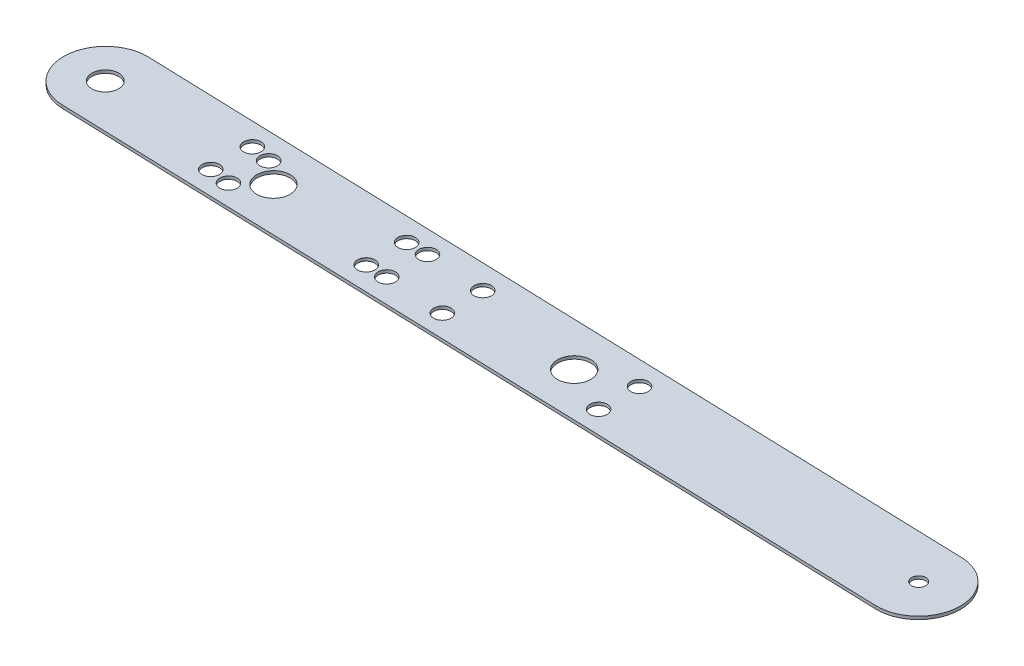
SolidWorks part; units mm, degrees
ref_plane "Front Plane" through (0, 0, 0) normal (0, 0, 1) x (1, 0, 0)
ref_plane "Top Plane" through (0, 0, 0) normal (0, 1, 0) x (1, 0, 0)
ref_plane "Right Plane" through (0, 0, 0) normal (1, 0, 0) x (0, 0, -1)
sketch "Sketch1" plane through (0, 0, 0) normal (0, 0, 1) x (1, 0, 0)
  line L0 (-78.6419, 31.6975) -> (161.4349, 101.4339) construction
  line L1 (-82.1287, 43.7013) -> (157.948, 113.4377)
  line L2 (-75.1551, 19.6937) -> (164.9217, 89.43)
  line L3 (-82.1287, 43.7013) -> (-75.1551, 19.6937) construction
  arc A0 (-82.1287, 43.7013) -> (-75.1551, 19.6937) centre (-78.6419, 31.6975) ccw
  arc A1 (164.9217, 89.43) -> (157.948, 113.4377) centre (161.4349, 101.4339) ccw
  point P2 (41.3965, 66.5657)
base flange "Base-Flange1" sketch "Sketch1" thickness 0.9 reverse thickness direction no parameters "D1"=1
sketch "Sketch7" plane through (0, 0, 0) normal (0, 0, 1) x (1, 0, 0)
  line L0 (-75.1551, 19.6937) -> (-82.1287, 43.7013) construction
  circle A0 centre (-78.6419, 31.6975) radius 1.75
extrude "Cut-Extrude1" cut sketch "Sketch7" against normal blind 10
hole_wizard "#6 (0.204) Diameter Slot1" positions "Sketch9" profile "Sketch8" size "#6" standard "ANSI Inch" slot yes end condition through all
sketch "Sketch9" plane through (0, 0, 0) normal (0, 0, 1) x (1, 0, 0)
  point P0 (-34.2115, 39.2524)
sketch "Sketch8" plane through (-34.2115, 39.2524, 0) normal (1, 0, 0) x (0, -1, 0)
  line L0 (0, 0) -> (0, 0.9)
  line L1 (0, 0.9) -> (2.5908, 0.9)
  line L2 (2.5908, 0.9) -> (2.5908, 0)
  line L5 (2.5908, 0) -> (0, 0)
  line L11 (0, -6.35) -> (0, 107.95) construction
  dimension "Thru Hole Dia." = 5.1816
  dimension "Thru Hole Depth" = 0.9
sketch "Sketch12" plane through (0, 0, -0.9) normal (0, 0, -1) x (-1, 0, 0)
  circle A0 centre (23.0553, 47.8102) radius 3.7522
hole_wizard "Ø1.0mm Dowel Slot1" positions "Sketch14" profile "Sketch13" size "Ø1.0" standard "ANSI Metric" slot yes end condition through all
sketch "Sketch14" plane through (0, 0, 0) normal (0, 0, 1) x (1, 0, 0)
  point P0 (-78.6419, 31.6975)
  point P3 (-78.6419, 31.6975)
sketch "Sketch13" plane through (-78.6419, 31.6975, 0) normal (1, 0, 0) x (0, -1, 0)
  line L0 (0, 0) -> (0, 0.9)
  line L1 (0, 0.9) -> (4, 0.9)
  line L2 (4, 0.9) -> (4, 0)
  line L5 (4, 0) -> (0, 0)
  line L11 (0, -6.35) -> (0, 107.95) construction
  dimension "Thru Hole Dia." = 8
  dimension "Thru Hole Depth" = 0.9
sketch "Sketch17" plane through (0, 0, 0) normal (0, 0, 1) x (1, 0, 0)
  circle A0 centre (39.3364, 65.6136) radius 3.75
hole_wizard "#19 (0.166) Diameter Slot2" positions "Sketch20" profile "Sketch19" size "#19" standard "ANSI Inch" slot yes end condition through all
sketch "Sketch20" plane through (0, 0, 0) normal (0, 0, 1) x (1, 0, 0)
  point P0 (161.4349, 101.4339)
sketch "Sketch19" plane through (161.4349, 101.4339, 0) normal (1, 0, 0) x (0, -1, 0)
  line L0 (0, 0) -> (0, 0.9)
  line L1 (0, 0.9) -> (2.1082, 0.9)
  line L2 (2.1082, 0.9) -> (2.1082, 0)
  line L5 (2.1082, 0) -> (0, 0)
  line L11 (0, -6.35) -> (0, 107.95) construction
  dimension "Thru Hole Dia." = 4.2164
  dimension "Thru Hole Depth" = 0.9
hole_wizard "Ø10.0mm Dowel Slot1" positions "Sketch22" profile "Sketch21" size "Ø10.0" standard "ANSI Metric" slot yes end condition through all
sketch "Sketch22" plane through (0, 0, -0.9) normal (0, 0, -1) x (-1, 0, 0)
  line L2 (90.6457, 28.2107) -> (-173.4387, 104.9207)
  circle A0 centre (78.6419, 31.6975) radius 4 construction
  arc A1 (75.1551, 19.6937) -> (82.1287, 43.7013) centre (78.6419, 31.6975) ccw construction
  arc A2 (-157.948, 113.4377) -> (-164.9217, 89.43) centre (-161.4349, 101.4339) ccw construction
  point P24 (28.994, 46.119)
  point P25 (-59.7569, 71.8989)
  dimension "D2" = 51.7
sketch "Sketch21" plane through (-28.994, 46.119, -0.9) normal (1, 0, 0) x (0, 1, 0)
  line L0 (0, 0) -> (0, 0.9)
  line L1 (0, 0.9) -> (5, 0.9)
  line L2 (5, 0.9) -> (5, 0)
  line L5 (5, 0) -> (0, 0)
  line L11 (0, -6.35) -> (0, 107.95) construction
  dimension "Thru Hole Dia." = 10
  dimension "Thru Hole Depth" = 0.9
hole_wizard "#6 (0.204) Diameter Slot7" positions "Sketch26" profile "Sketch25" size "#6" standard "ANSI Inch" slot yes end condition through all
sketch "Sketch26" plane through (0, 0, -0.9) normal (0, 0, -1) x (-1, 0, 0)
  point P0 (37.4542, 50.4528)
sketch "Sketch25" plane through (-37.4542, 50.4528, -0.9) normal (1, 0, 0) x (0, 1, 0)
  line L0 (0, 0) -> (0, 0.9)
  line L1 (0, 0.9) -> (2.5908, 0.9)
  line L2 (2.5908, 0.9) -> (2.5908, 0)
  line L5 (2.5908, 0) -> (0, 0)
  line L11 (0, -6.35) -> (0, 107.95) construction
  dimension "Thru Hole Dia." = 5.1816
  dimension "Thru Hole Depth" = 0.9
hole_wizard "#6 (0.204) Diameter Slot9" positions "Sketch30" profile "Sketch29" size "#6" standard "ANSI Inch" slot yes end condition through all
sketch "Sketch30" plane through (0, 0, 0) normal (0, 0, 1) x (1, 0, 0)
  point P0 (28.6223, 56.9997)
  point P2 (25.3744, 68.2854)
  point P4 (74.7726, 70.2473)
  point P6 (71.479, 81.6873)
sketch "Sketch29" plane through (28.6223, 56.9997, 0) normal (1, 0, 0) x (0, -1, 0)
  line L0 (0, 0) -> (0, 0.9)
  line L1 (0, 0.9) -> (2.5908, 0.9)
  line L2 (2.5908, 0.9) -> (2.5908, 0)
  line L5 (2.5908, 0) -> (0, 0)
  line L11 (0, -6.35) -> (0, 107.95) construction
  dimension "Thru Hole Dia." = 5.1816
  dimension "Thru Hole Depth" = 0.9
hole_wizard "#6 (0.204) Diameter Slot10" positions "Sketch32" profile "Sketch31" size "#6" standard "ANSI Inch" slot yes end condition through all
sketch "Sketch32" plane through (0, 0, -0.9) normal (0, 0, -1) x (-1, 0, 0)
  point P0 (-8.5953, 62.8981)
  point P2 (-11.9118, 51.6025)
sketch "Sketch31" plane through (8.5953, 62.8981, -0.9) normal (1, 0, 0) x (0, 1, 0)
  line L0 (0, 0) -> (0, 0.9)
  line L1 (0, 0.9) -> (2.5908, 0.9)
  line L2 (2.5908, 0.9) -> (2.5908, 0)
  line L5 (2.5908, 0) -> (0, 0)
  line L11 (0, -6.35) -> (0, 107.95) construction
  dimension "Thru Hole Dia." = 5.1816
  dimension "Thru Hole Depth" = 0.9
move or copy body "Body-Move/Copy1" bodies to move or copy 115 copy no rotation origin (0, 66.5657, -0.45) rotation axis (1, 0, 0) rotation angle 90
move or copy body "Body-Move/Copy2" bodies to move or copy 116 copy no rotation origin (39.0674, -1.3406, -0.1537) rotation axis (0.0343, 0.9994, -0.0044) rotation angle 14.509
sketch "Sketch33" plane through (0.1446, 66.1973, 0.5593) normal (-0.0022, -1, -0.0084) x (-1, 0.0022, 0)
  line L0 (84.0645, -7.7786) -> (83.3238, 17.2104) construction
  line L1 (83.3238, 17.2104) -> (-166.5664, 9.8034) construction
  arc A0 (84.0645, -7.7786) -> (83.3238, 17.2104) centre (83.6942, 4.7159) ccw construction
hole_wizard "#6 (0.204) Diameter Slot11" positions "Sketch35" profile "Sketch34" size "#6" standard "ANSI Inch" slot yes end condition through all
sketch "Sketch35" plane through (0.1446, 66.1973, 0.5593) normal (-0.0022, -1, -0.0084) x (-1, 0.0022, 0)
  point P0 (-2.4332, -3.6166)
  point P2 (-2.759, 8.1038)
  point P4 (45.2635, -2.2566)
  point P6 (44.814, 9.6774)
sketch "Sketch34" plane through (2.5778, 66.1614, 4.1757) normal (0.7071, -0.0075, 0.7071) x (0.7071, 0.0044, -0.7071)
  line L0 (0, 0) -> (0, 1.7505)
  line L1 (0, 1.7505) -> (2.5908, 1.7505)
  line L2 (2.5908, 1.7505) -> (2.5908, 0)
  line L5 (2.5908, 0) -> (0, 0)
  line L11 (0, -6.35) -> (0, 107.95) construction
  dimension "Thru Hole Dia." = 5.1816
  dimension "Thru Hole Depth" = 1.7505
sketch "Bend-Lines1" plane through (0, 0, 0) normal (0, 1, 0) x (1, 0, 0)
sketch "Bounding-Box1" plane through (0, 0, 0) normal (0, 1, 0) x (1, 0, 0)
sheet metal parameters "Sheet-Metal1" thickness 0.9 parameters "D1"=3
flat pattern "Flat-Pattern1" [suppressed]
sketch "Bend-Lines2" plane through (0, 0, 0) normal (0, 1, 0) x (1, 0, 0)
sketch "Bounding-Box2" [suppressed] plane through (0, 0, 0) normal (0, 1, 0) x (1, 0, 0)
sheet metal parameters "Sheet-Metal2" thickness 0.9 parameters "D1"=3
flat pattern "Flat-Pattern1"
sketch "Bend-Lines2" plane through (0, 0, 0) normal (0, 1, 0) x (1, 0, 0)
sketch "Bounding-Box2" [suppressed] plane through (0, 0, 0) normal (0, 1, 0) x (1, 0, 0)
sheet metal parameters "Sheet-Metal3" thickness 0.9 parameters "D1"=3
flat pattern "Flat-Pattern1"
sketch "Bend-Lines2" plane through (0, 0, 0) normal (0, 1, 0) x (1, 0, 0)
sketch "Bounding-Box2" [suppressed] plane through (0, 0, 0) normal (0, 1, 0) x (1, 0, 0)
sheet metal parameters "Sheet-Metal6" thickness 0.9 parameters "D1"=3
flat pattern "Flat-Pattern1"
sketch "Bend-Lines2" plane through (0, 0, 0) normal (0, 1, 0) x (1, 0, 0)
sketch "Bounding-Box2" [suppressed] plane through (0, 0, 0) normal (0, 1, 0) x (1, 0, 0)
sheet metal parameters "Sheet-Metal9" thickness 0.9 parameters "D1"=3
flat pattern "Flat-Pattern1"
sketch "Bend-Lines2" plane through (0, 0, 0) normal (0, 1, 0) x (1, 0, 0)
sketch "Bounding-Box2" [suppressed] plane through (0, 0, 0) normal (0, 1, 0) x (1, 0, 0)
sheet metal parameters "Sheet-Metal10" thickness 0.9 parameters "D1"=3
flat pattern "Flat-Pattern1"
sketch "Bend-Lines2" plane through (0, 0, 0) normal (0, 1, 0) x (1, 0, 0)
sketch "Bounding-Box2" [suppressed] plane through (0, 0, 0) normal (0, 1, 0) x (1, 0, 0)
sheet metal parameters "Sheet-Metal12" thickness 0.9 parameters "D1"=3
flat pattern "Flat-Pattern1"
sketch "Bend-Lines2" plane through (0, 0, 0) normal (0, 1, 0) x (1, 0, 0)
sketch "Bounding-Box2" [suppressed] plane through (0, 0, 0) normal (0, 1, 0) x (1, 0, 0)
sheet metal parameters "Sheet-Metal14" thickness 0.9 parameters "D1"=3
flat pattern "Flat-Pattern1"
sketch "Bend-Lines2" plane through (0, 0, 0) normal (0, 1, 0) x (1, 0, 0)
sketch "Bounding-Box2" [suppressed] plane through (0, 0, 0) normal (0, 1, 0) x (1, 0, 0)
sheet metal parameters "Sheet-Metal15" thickness 0.9 parameters "D1"=3
flat pattern "Flat-Pattern1"
sketch "Bend-Lines2" plane through (0, 0, 0) normal (0, 1, 0) x (1, 0, 0)
sketch "Bounding-Box2" [suppressed] plane through (0, 0, 0) normal (0, 1, 0) x (1, 0, 0)
sheet metal parameters "Sheet-Metal16" thickness 0.9 parameters "D1"=3
flat pattern "Flat-Pattern1"
sketch "Bend-Lines2" plane through (0, 0, 0) normal (0, 1, 0) x (1, 0, 0)
sketch "Bounding-Box2" [suppressed] plane through (0, 0, 0) normal (0, 1, 0) x (1, 0, 0)
sheet metal parameters "Sheet-Metal17" thickness 0.9 parameters "D1"=3
flat pattern "Flat-Pattern1"
sketch "Bend-Lines2" plane through (0, 0, 0) normal (0, 1, 0) x (1, 0, 0)
sketch "Bounding-Box2" [suppressed] plane through (0, 0, 0) normal (0, 1, 0) x (1, 0, 0)
sheet metal parameters "Sheet-Metal18" thickness 0.9 parameters "D1"=3
flat pattern "Flat-Pattern1"
sketch "Bend-Lines2" plane through (0, 0, 0) normal (0, 1, 0) x (1, 0, 0)
sketch "Bounding-Box2" [suppressed] plane through (0, 0, 0) normal (0, 1, 0) x (1, 0, 0)
